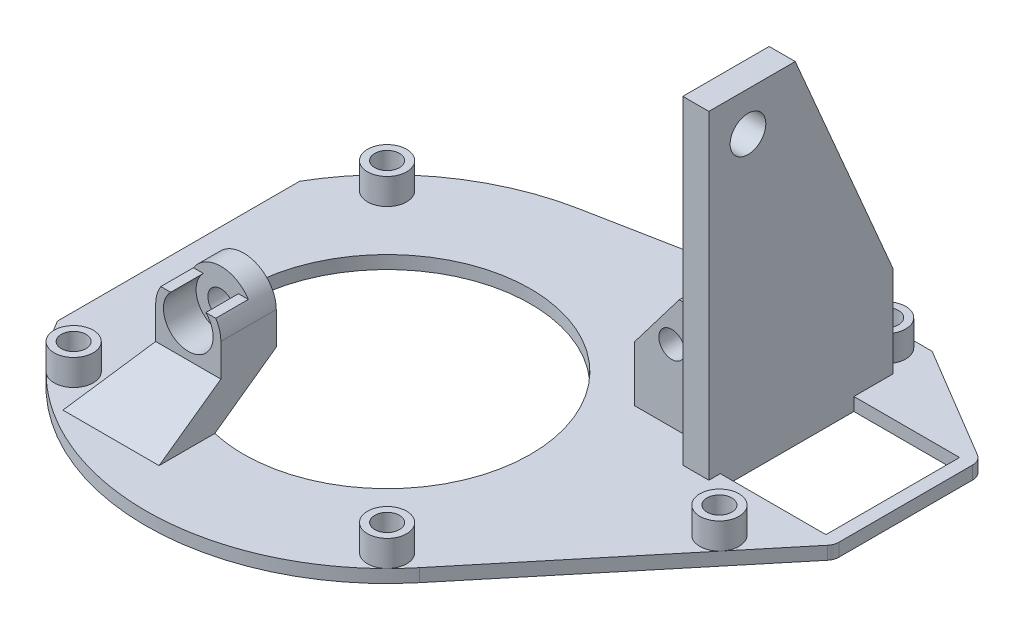
SolidWorks part; units mm, degrees
ref_plane "Front Plane" through (0, 0, 0) normal (0, 0, 1) x (1, 0, 0)
ref_plane "Top Plane" through (0, 0, 0) normal (0, 1, 0) x (1, 0, 0)
ref_plane "Right Plane" through (0, 0, 0) normal (1, 0, 0) x (0, 0, -1)
sketch "Layout" plane through (0, 0, 0) normal (0, 1, 0) x (1, 0, 0)
  line L0 (-22.5, -12) -> (-2.5, -12) construction
  line L1 (-22.5, -15.5) -> (-2.5, -15.5) construction
  line L2 (-10, -12) -> (-10, -15.5) construction
  line L3 (35.1095, 44.5) -> (35.1096, 10.25) construction
  line L4 (39.1095, 44.5) -> (39.1095, 10.25) construction
  line L5 (-22.5, -12) -> (-22.5, -15.5) construction
  line L6 (-2.5, -12) -> (-2.5, -15.5) construction
  line L7 (35.1095, 16.2392) -> (39.1095, 16.2392) construction
  line L8 (35.1095, 44.5) -> (39.1095, 44.5) construction
  line L9 (35.1096, 10.25) -> (39.1095, 10.25) construction
  line L10 (35.1095, 20.05) -> (23.5128, 20.05) construction
  line L11 (23.5128, 20.05) -> (23.5128, 14.45) construction
  line L12 (23.5128, 14.45) -> (35.1096, 14.45) construction
  line L13 (39.1095, 12) -> (55.3188, 12) construction
  line L14 (55.3188, 12) -> (55.3188, 32.5) construction
  line L15 (55.3188, 32.5) -> (39.1095, 32.5) construction
  line L16 (29.2267, 20.05) -> (29.2267, 14.45) construction
  line L17 (-35, 35.6086) -> (-35, -36.5552) construction
  dimension "D1" = 12
  dimension "D2" = 10
  dimension "D3" = 3.5
  dimension "D4" = 4
  dimension "D5" = 12.5
  dimension "D6" = 7.5
  dimension "D7" = 45.1095
  dimension "D8" = 28.2392
  dimension "D9" = 22.25
  dimension "D10" = 34.25
  dimension "D11" = 4.2
  dimension "D12" = 5.6
  dimension "D13" = 1.75
  dimension "D14" = 20.5
  dimension "D15" = 16.2093
  dimension "D16" = 5.8828
  dimension "D17" = 25
sketch "Sketch2" plane through (0, 0, 0) normal (0, 1, 0) x (1, 0, 0)
  line L0 (35.1095, 44.5) -> (-7.0457, 36.323)
  line L1 (39.1095, 44.5) -> (56.3436, 34.2175)
  line L2 (57.3188, 32.5) -> (57.3188, 12)
  line L3 (28.5223, -23.5685) -> (56.8606, 10.726)
  line L4 (35.1095, 44.5) -> (39.1095, 44.5)
  line L5 (39.1095, 12) -> (55.3188, 12)
  line L6 (39.1095, 12) -> (39.1095, 32.5)
  line L7 (39.1095, 32.5) -> (55.3188, 32.5)
  line L8 (55.3188, 12) -> (55.3188, 32.5)
  line L9 (-35.7267, 35.7267) -> (35.7267, -35.7267) construction
  line L10 (0, 0) -> (-29.9076, -29.9076) construction
  line L11 (-32, 18.5742) -> (-32, -18.5742)
  line L12 (-35, 35.6086) -> (-35, -36.5552) construction
  circle A0 centre (0, 0) radius 22
  arc A1 (-7.0457, 36.323) -> (-32, 18.5742) centre (0, 0) ccw
  arc A2 (57.3188, 32.5) -> (56.3436, 34.2175) centre (55.3188, 32.5) ccw
  arc A3 (56.8606, 10.726) -> (57.3188, 12) centre (55.3188, 12) ccw
  circle A4 centre (0, 0) radius 37 construction
  arc A9 (-32, -18.5742) -> (28.5223, -23.5685) centre (0, 0) ccw
  point P24 (0, 0)
  point P34 (-26.163, 26.163)
  point P35 (-26.163, -26.163)
  point P36 (26.163, -26.163)
  dimension "D1" = 44
  dimension "D8" = 3
  dimension "D2" = 15
extrude "Boss-Extrude1" add sketch "Sketch2" against normal blind 2
ref_plane "Plane1" through (0, 0, -14.45) normal (0, 0, 1) x (1, 0, 0)
sketch "Sketch6" plane through (0, 0, -14.45) normal (0, 0, 1) x (1, 0, 0)
  line L0 (23.5128, 0) -> (23.5128, 8.5)
  line L1 (23.5128, 0) -> (35.1096, 0) construction
  line L2 (35.1095, 0) -> (23.5128, 0) construction
  line L3 (23.5128, 8.5) -> (30.3596, 17.5)
  line L4 (30.3596, 17.5) -> (35.1096, 17.5)
  line L5 (35.1096, 17.5) -> (35.1096, 0)
  line L6 (35.1095, 0) -> (39.1095, 0) construction
  line L7 (35.1096, 0) -> (23.5128, 0)
  circle A0 centre (29.2295, 11) radius 2
  dimension "D4" = 4
  dimension "D1" = 8.5
  dimension "D2" = 17.5
  dimension "D3" = 4.75
  dimension "D5" = 11
  dimension "D6" = 5.88
extrude "Boss-Extrude3" add sketch "Sketch6" against normal up to vertex (5.6 mm away) up to point (29.2267, 0, -20.05)
ref_plane "Plane2" through (35.1096, 0, 0) normal (1, 0, 0) x (0, 0, -1)
sketch "Sketch7" plane through (35.1096, 0, 0) normal (1, 0, 0) x (0, 0, -1)
  line L0 (44.5, 0) -> (10.25, 0) construction
  line L1 (44.5, 0) -> (10.25, 0)
  line L2 (10.25, 0) -> (10.25, 49)
  line L3 (10.25, 49) -> (23.5, 49)
  line L4 (23.5, 49) -> (44.5, 0)
  circle A0 centre (16.25, 43) radius 2.739
  dimension "D3" = 5.478
  dimension "D1" = 49
  dimension "D2" = 13.25
  dimension "D4" = 6
  dimension "D5" = 43
extrude "Boss-Extrude4" add sketch "Sketch7" along normal up to vertex (4 mm away) up to point (39.1095, 0, -10.25)
ref_plane "Plane3" through (0, 0, 15.5) normal (0, 0, 1) x (1, 0, 0)
sketch "Sketch9" plane through (0, 0, 15.5) normal (0, 0, 1) x (1, 0, 0)
  line L0 (-15, 11.75) -> (-15, 6.75)
  line L1 (-15, 6.75) -> (-10, 6.75)
  line L2 (-10, 6.75) -> (-5, 6.75)
  line L3 (-5, 6.75) -> (-5, 11.75)
  circle A0 centre (-10, 11.75) radius 2
  arc A1 (-5, 11.75) -> (-15, 11.75) centre (-10, 11.75) ccw
  circle A2 centre (-10, 11.75) radius 5 construction
  point P0 (-10, 0)
  dimension "D1" = 4
  dimension "D3" = 3
  dimension "D2" = 11.75
extrude "Boss-Extrude5" add sketch "Sketch9" against normal up to vertex (3.5 mm away) and the other way blind 5 separate body up to point (-10, 0, 12)
sketch "Sketch10" plane through (0, 0, 0) normal (0, 1, 0) x (1, 0, 0)
  line L0 (-5, -12) -> (-5, -20.5) construction
  line L1 (-5, -12) -> (-5, -20.5)
  line L3 (-5, -21.4243) -> (-19.7493, -21.4243)
  line L4 (-5, -21.4243) -> (-5, -29.9815)
  line L5 (-5, -29.9815) -> (-19.7493, -29.9815)
  line L6 (-19.7493, -21.4243) -> (-19.7493, -29.9815)
  circle A0 centre (0, 0) radius 22 construction
loft "Loft4" add section face at (-10, 6.75, 16.25) section "Sketch10" connector at (-5, 6.75, 20.5) connector at (-5, 0, 29.9815)
sketch "Sketch11" plane through (0, 0, 20.5) normal (0, 0, 1) x (1, 0, 0)
  circle A0 centre (-10, 11.75) radius 3.81
  dimension "D1" = 7.62
extrude "Cut-Extrude1" cut sketch "Sketch11" against normal up to surface (5 mm away) up to plane "Plane3"
sketch "Sketch13" plane through (39.1095, 0, 0) normal (1, 0, 0) x (0, 0, -1)
  line L0 (44.5, 0) -> (38.5, 0)
  line L1 (44.5, 0) -> (10.25, 0) construction
  line L2 (38.5, 0) -> (38.5, 14)
  line L3 (44.5, 0) -> (23.5, 49) construction
  line L4 (38.5, 14) -> (44.5, 0)
  dimension "D1" = 6
extrude "Cut-Extrude2" cut sketch "Sketch13" against normal up to next
sketch "Sketch12" plane through (0, 0, 0) normal (0, 1, 0) x (1, 0, 0)
  line L0 (0, 0) -> (-26.163, 26.163) construction
  line L1 (0, 0) -> (-26.163, -26.163) construction
  line L2 (0, 0) -> (26.163, -26.163) construction
  line L3 (28.5223, -23.5685) -> (56.8606, 10.726) construction
  line L4 (39.1095, 12) -> (55.3188, 12) construction
  line L6 (35.1096, 44.5) -> (-7.0457, 36.323) construction
  line L7 (39.1095, 44.5) -> (39.1095, 10.25) construction
  arc A0 (-7.0457, 36.323) -> (-32, 18.5742) centre (0, 0) ccw construction
  arc A1 (-32, -18.5742) -> (28.5223, -23.5685) centre (0, 0) ccw construction
  circle A2 centre (-24.0416, 24.0416) radius 3
  circle A3 centre (-24.0416, -24.0416) radius 3
  circle A4 centre (24.0416, -24.0416) radius 3
  circle A5 centre (47.2142, 3.7618) radius 3
  circle A6 centre (35.1095, 41.4441) radius 3
  point P26 (47.2142, 12)
  dimension "D1" = 6
  dimension "D2" = 3
  dimension "D3" = 3
  dimension "D4" = 3
  dimension "D5" = 3
  dimension "D6" = 4
  dimension "D7" = 3
extrude "Boss-Extrude9" add sketch "Sketch12" along normal blind 4
sketch "Sketch14" plane through (0, 4, 0) normal (0, 1, 0) x (1, 0, 0)
  circle A0 centre (-24.0416, 24.0416) radius 1.9
  circle A1 centre (35.1095, 41.4441) radius 1.9
  circle A2 centre (47.2142, 3.7618) radius 1.9
  circle A3 centre (24.0416, -24.0416) radius 1.9
  circle A4 centre (-24.0416, -24.0416) radius 1.9
  dimension "D1" = 3.8
extrude "Cut-Extrude3" cut sketch "Sketch14" against normal through all
sketch "Sketch18" plane through (0, 0, 20.5) normal (0, 0, 1) x (1, 0, 0)
  line L0 (-10, 11.75) -> (-12.6941, 14.4441)
  line L1 (-12.6941, 14.4441) -> (-14.2121, 14.4441)
  line L2 (-10, 11.75) -> (-7.3059, 14.4441)
  line L3 (-7.3059, 14.4441) -> (-5.7879, 14.4441)
  arc A1 (-5, 11.75) -> (-15, 11.75) centre (-10, 11.75) ccw construction
  arc A3 (-5.7879, 14.4441) -> (-14.2121, 14.4441) centre (-10, 11.75) ccw
extrude "Cut-Extrude5" cut sketch "Sketch18" against normal up to surface (5 mm away) up to face at (-8, 11.75, 15.5)
